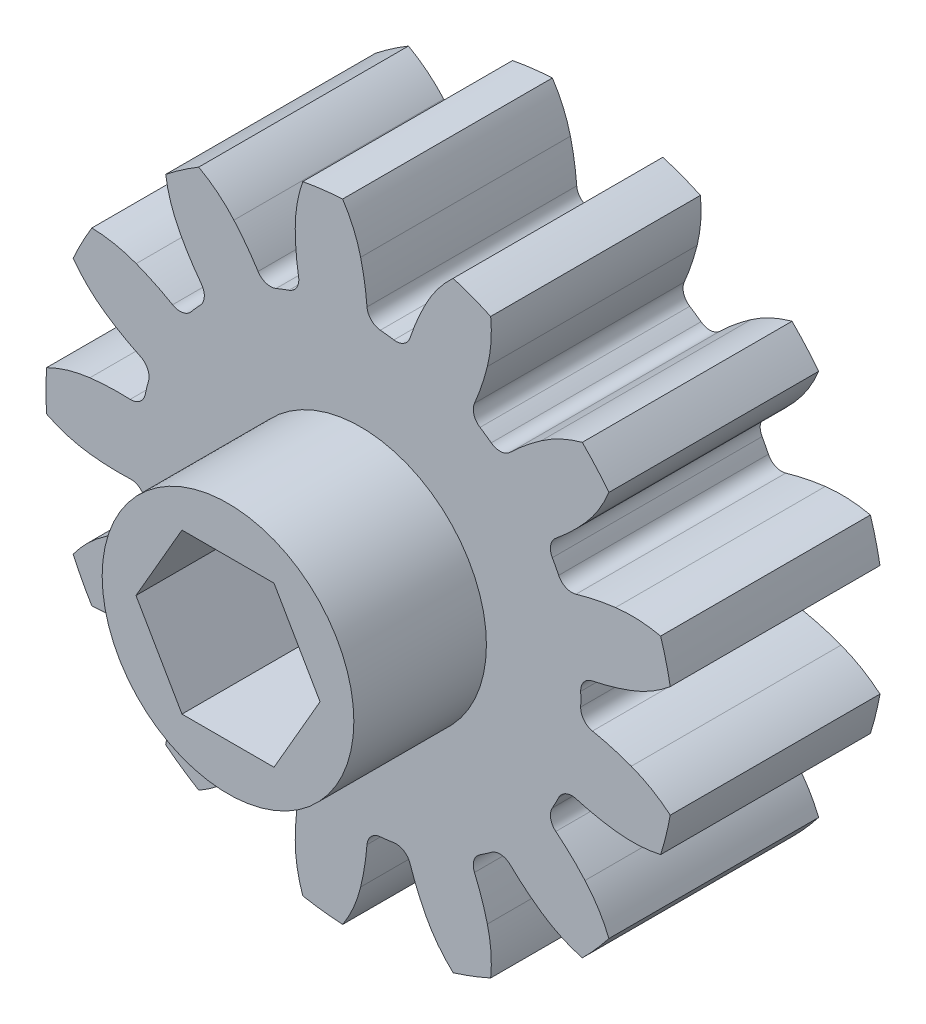
SolidWorks part; units mm, degrees
material "PLA/ABS"
ref_plane "Front" through (0, 0, 0) normal (0, 0, 1) x (1, 0, 0)
ref_plane "Top" through (0, 0, 0) normal (0, 1, 0) x (1, 0, 0)
ref_plane "Right" through (0, 0, 0) normal (1, 0, 0) x (0, 0, -1)
sketch "Sketch1" plane through (0, 0, 0) normal (0, 0, 1) x (1, 0, 0)
  line L0 (0, 0) -> (8.255, 0) construction
  line L1 (8.255, 0) -> (9.525, 0) construction
  circle A0 centre (0, 0) radius 8.255 construction
  circle A1 centre (0, 0) radius 9.525
  dimension "D1" = 16.51
  dimension "D2" = 1.27
extrude "Round Stock" add sketch "Sketch1" along normal mid plane 6.35
sketch "Sketch2" plane through (0, 0, 3.175) normal (0, 0, 1) x (1, 0, 0)
  line L0 (0, 0) -> (6.6675, 0) construction
  line L1 (6.6675, 0) -> (8.255, 0) construction
  line L2 (0, 0) -> (-9.525, 0) construction
  line L3 (0, 0) -> (-8.434, -4.4265) construction
  line L4 (-8.6992, -3.8793) -> (-7.7195, -2.9249) construction
  line L5 (-7.7195, -2.9249) -> (-6.3199, -2.1249) construction
  line L6 (-9.5056, -0.6078) -> (-8.1945, -0.9976) construction
  line L7 (-8.1945, -0.9976) -> (-6.5834, -1.0555) construction
  line L8 (-7.2559, -3.8082) -> (-7.7195, -2.9249) construction
  line L9 (-8.1945, -0.9976) -> (-8.1945, 0) construction
  line L12 (0, 0) -> (-8.1945, -0.9976) construction
  line L13 (0, 0) -> (-7.7195, -2.9249) construction
  line L14 (-7.7195, -2.9249) -> (-6.0358, -7.3685) construction
  line L15 (-8.1945, -0.9976) -> (-8.7688, 3.7195) construction
  line L16 (-7.7195, -2.9249) -> (-8.1945, -0.9976) construction
  line L17 (-6.4738, -1.5956) -> (-6.5834, -1.0555) construction
  line L18 (-6.4738, -1.5956) -> (-6.3199, -2.1249) construction
  circle A0 centre (0, 0) radius 8.255 construction
  circle A1 centre (0, 0) radius 6.6675 construction
  circle A2 centre (0, 0) radius 9.525 construction
  arc A3 (-8.6992, -3.8793) -> (-9.5056, -0.6078) centre (0, 0) cw
  arc A4 (-6.3199, -2.1249) -> (-6.5834, -1.0555) centre (0, 0) cw construction
  arc A6 (-8.6992, -3.8793) -> (-7.7195, -2.9249) centre (-5.4661, -6.218) cw
  arc A7 (-9.5056, -0.6078) -> (-8.1945, -0.9976) centre (-7.7296, 2.9656) ccw
  arc A8 (-7.7195, -2.9249) -> (-6.6596, -2.3175) centre (-3.3876, -9.2555) cw
  arc A9 (-8.1945, -0.9976) -> (-6.9738, -1.0428) centre (-7.3008, 6.621) ccw
  arc A10 (-6.6596, -2.3175) -> (-6.4211, -1.7957) centre (-6.8492, -1.9154) ccw
  arc A11 (-6.9738, -1.0428) -> (-6.5201, -1.394) centre (-6.9548, -1.4869) cw
  arc A12 (-6.4211, -1.7957) -> (-6.5201, -1.394) centre (0, 0) cw
  dimension "D6" = 16.51
  dimension "D9" = 0.4445
  dimension "D12" = 3.9903
  dimension "D2" = 1.5875
  dimension "D3" = 27.692
  dimension "D4" = 0.9976
  dimension "D5" = 0.9976
  dimension "D11" = 1.985
  dimension "D8" = 14.5
  dimension "D7" = 14.5
  dimension "D14" = 9
  dimension "D15" = 9
extrude "Single Tooth" cut sketch "Sketch2" against normal through all
ref_axis "Axis" through (0, 0, 50) along (0, 0, -1)
pattern_circular "Tooth Pattern" count 13 over 360 about axis through (0, 0, 50) along (0, 0, -1) of "Single Tooth"
sketch "Sketch4" plane through (0, 0, 3.175) normal (0, 0, 1) x (1, 0, 0)
  circle A0 centre (0, 0) radius 3.1039
  dimension "D1" = 6.2078
extrude "TopBearingBoss" [suppressed] add sketch "Sketch4" along normal blind 0.635
mirror "BottomBearingBoss" [suppressed] about plane through (0, 0, 0) normal (0, 0, 1)
sketch "Sketch6" [suppressed] plane through (0, 0, 0) normal (0, 0, 1) x (1, 0, 0)
  line L1 (1.4005, 2.4257) -> (-1.4005, 2.4257)
  line L2 (-1.4005, 2.4257) -> (-2.801, 0)
  line L3 (-2.801, 0) -> (-1.4005, -2.4257)
  line L4 (-1.4005, -2.4257) -> (1.4005, -2.4257)
  line L5 (1.4005, -2.4257) -> (2.801, 0)
  line L6 (2.801, 0) -> (1.4005, 2.4257)
  circle A0 centre (0, 0) radius 2.4257 construction
  circle A1 centre (0, 0) radius 2.4257 construction
extrude "Hex" [suppressed] cut sketch "Sketch6" against normal through all both and the other way through all
sketch "Sketch7" plane through (0, 0, -3.175) normal (0, 0, -1) x (-1, 0, 0)
  line L1 (1.3931, -2.413) -> (2.7863, 0)
  line L2 (2.7863, 0) -> (1.3931, 2.413)
  line L3 (1.3931, 2.413) -> (-1.3931, 2.413)
  line L4 (-1.3931, 2.413) -> (-2.7863, 0)
  line L5 (-2.7863, 0) -> (-1.3931, -2.413)
  line L6 (-1.3931, -2.413) -> (1.3931, -2.413)
  circle A0 centre (0, 0) radius 2.413 construction
  dimension "D1" = 4.826
extrude "Cut-Extrude1" cut sketch "Sketch7" against normal through all
sketch "Sketch8" plane through (0, 0, 3.175) normal (0, 0, 1) x (1, 0, 0)
  line L6 (-1.3931, -2.413) -> (1.3931, -2.413)
  line L7 (-2.7863, 0) -> (-1.3931, -2.413)
  line L8 (-1.3931, 2.413) -> (-2.7863, 0)
  line L9 (1.3931, 2.413) -> (-1.3931, 2.413)
  line L10 (2.7863, 0) -> (1.3931, 2.413)
  line L11 (1.3931, -2.413) -> (2.7863, 0)
  line L12 (-1.3931, -2.413) -> (1.3931, -2.413)
  line L13 (-2.7863, 0) -> (-1.3931, -2.413)
  line L14 (-1.3931, 2.413) -> (-2.7863, 0)
  line L15 (1.3931, 2.413) -> (-1.3931, 2.413)
  line L16 (2.7863, 0) -> (1.3931, 2.413)
  line L17 (1.3931, -2.413) -> (2.7863, 0)
  circle A0 centre (0, 0) radius 3.81
  dimension "D2" = 7.62
  dimension "D1" = 0
extrude "Boss-Extrude1" add sketch "Sketch8" along normal blind 4.0132
equation "\"N_teeth\"= \"No_Teeth\""
equation "\"pitch_diameter\"= \"N_teeth\" / \"Pitch\""
equation "\"Pd\"=\"N_teeth\"/\"pitch_diameter\""
equation "\"addendum\"=1.000/\"Pd\""
equation "\"face_width\"=0.25"
equation "\"deddendum\"=1.250/\"Pd\""
equation "\"D3@Sketch2\" = 360/\"N_teeth\""
equation "\"tooth_thickness\"=1.571/\"Pd\""
equation "\"D4@Sketch2\" = \"tooth_thickness\"/2"
equation "\"D5@Sketch2\" = \"tooth_thickness\"/2"
equation "\"Pressure_Angle\"= iif ( \"Pitch\" = 20 , 14.500000 , iif ( \"Pitch\" = 32 , 20 , 20 ) )"
equation "\"base_fillet\"=0.35/\"Pd\""
equation "\"D12@Sketch2\" = 2*\"tooth_thickness\""
equation "\"hub_projection\"=0.250000"
equation "\"sss_diam\"= 0.062500"
equation "\"D1@Sketch1\"=\"pitch_diameter\""
equation "\"D2@Sketch1\"=\"addendum\""
equation "\"D1@Round Stock\" = \"face_width\""
equation "\"D2@Sketch2\"=\"deddendum\""
equation "\"D6@Sketch2\"=\"pitch_diameter\""
equation "\"D7@Sketch2\"=\"Pressure_Angle\""
equation "\"D8@Sketch2\"=\"D7@Sketch2\""
equation "\"D9@Sketch2\"=\"base_fillet\""
equation "\"D1@Tooth Pattern\" = \"N_teeth\""
equation "\"Pitch\"= \"GearPitch\""
equation "\"BossDia\"= \"BoreDia\" * 1.3"
equation "\"Hex\"= iif ( \"HexBore\" = 1 , \"unsuppressed\" , \"suppressed\" )"
equation "\"TopBearingBoss\" = iif ( \"Bearing_Boss\" = 0 , \"suppressed\" , \"unsuppressed\" )"
equation "\"BottomBearingBoss\"= iif ( \"Bearing_Boss\" > 1 , \"unsuppressed\" , \"suppressed\" )"
equation "\"D1@Sketch4\"=\"BossDia\""
equation "\"ToothCount\"= iif ( \"No_Teeth\" < 22 , \"suppressed\" , \"unsuppressed\" )"
